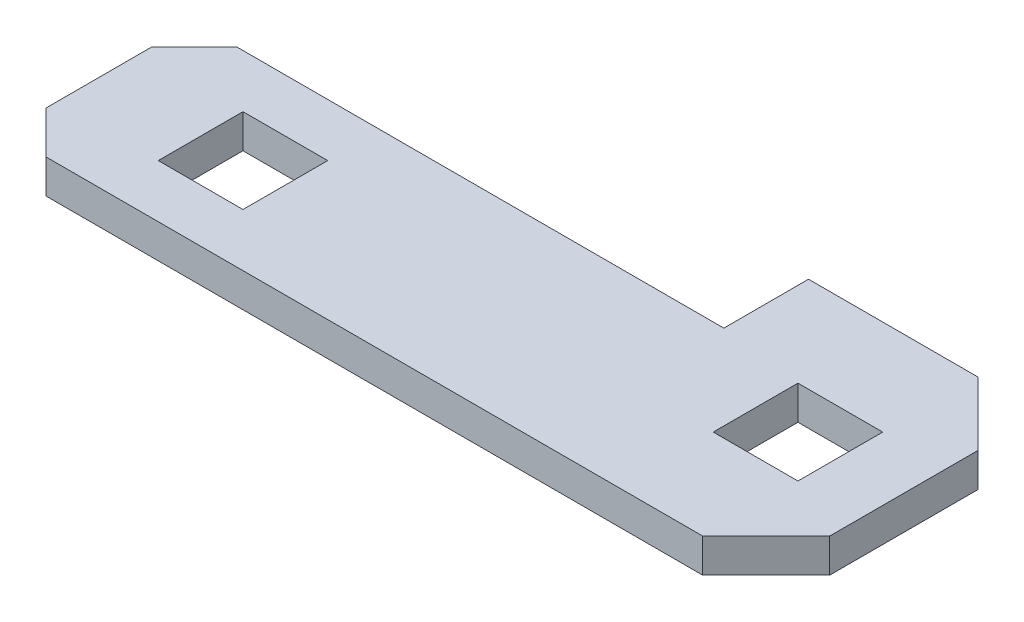
SolidWorks part; units mm, degrees
material "Медь"
ref_plane "Спереди" through (0, 0, 0) normal (0, 0, 1) x (1, 0, 0)
ref_plane "Сверху" through (0, 0, 0) normal (0, 1, 0) x (1, 0, 0)
ref_plane "Справа" through (0, 0, 0) normal (1, 0, 0) x (0, 0, -1)
sketch "Эскиз1" plane through (0, 0, 0) normal (0, 1, 0) x (1, 0, 0)
  line L0 (0, 0) -> (0, 4.5)
  line L1 (0, 4.5) -> (12.5, 4.5)
  line L2 (12.5, 4.5) -> (12.5, 6.5)
  line L3 (12.5, 6.5) -> (18, 6.5)
  line L4 (18, 6.5) -> (18, 0)
  line L5 (18, 0) -> (0, 0)
  line L6 (3.4, 3.25) -> (3.4, 4.5) construction
  line L7 (2.4, 1.25) -> (4.4, 1.25)
  line L8 (2.4, 1.25) -> (2.4, 3.25)
  line L9 (2.4, 3.25) -> (4.4, 3.25)
  line L10 (4.4, 1.25) -> (4.4, 3.25)
  line L11 (3.4, 3.25) -> (3.4, 1.25) construction
  line L12 (2.4, 2.25) -> (4.4, 2.25) construction
  line L13 (3.4, 1.25) -> (3.4, 0) construction
  line L14 (15.5, 4.25) -> (15.5, 6.5) construction
  line L15 (14.5, 2.25) -> (16.5, 2.25)
  line L16 (14.5, 2.25) -> (14.5, 4.25)
  line L17 (14.5, 4.25) -> (16.5, 4.25)
  line L18 (16.5, 2.25) -> (16.5, 4.25)
  line L19 (15.5, 4.25) -> (15.5, 2.25) construction
  line L20 (14.5, 3.25) -> (16.5, 3.25) construction
  line L21 (15.5, 2.25) -> (15.5, 0) construction
  point P8 (3.4, 2.25)
  point P13 (15.5, 3.25)
  dimension "D1" = 4.5
  dimension "D2" = 18
  dimension "D3" = 5.5
  dimension "D4" = 6.5
  dimension "D5" = 2
  dimension "D6" = 12.1
  dimension "D7" = 2.5
base flange "Базовая кромка1" sketch "Эскиз1" thickness 0.8 reverse thickness direction no parameters "D1"=0.5
chamfer "Фаска1" distance 1 angle 45 2 edges at (0, -0.4, -4.5) (0, -0.4, 0)
chamfer "Фаска2" distance 1.5 angle 45 2 edges at (18, -0.4, -6.5) (18, -0.4, 0)
sketch "Сгиб-Линии1" [suppressed] plane through (0, 0, 0) normal (0, 1, 0) x (1, 0, 0)
sketch "Граничная рамка1" [suppressed] plane through (0, 0, 0) normal (0, 1, 0) x (1, 0, 0)
sheet metal parameters "Листовой металл1" thickness 0.8 parameters "D1"=0.5
flat pattern "Развертка1" [suppressed]
sketch "Сгиб-Линии2" plane through (0, 0, 0) normal (0, 1, 0) x (1, 0, 0)
sketch3d "Граничная рамка2" [suppressed]
  line L0 (18, 6.5, 0) -> (0, 6.5, 0) construction
  line L1 (18, 0, 0) -> (0, 0, 0) construction
  line L2 (18, 6.5, 0) -> (18, 0, 0) construction
  line L3 (0, 6.5, 0) -> (0, 0, 0) construction
